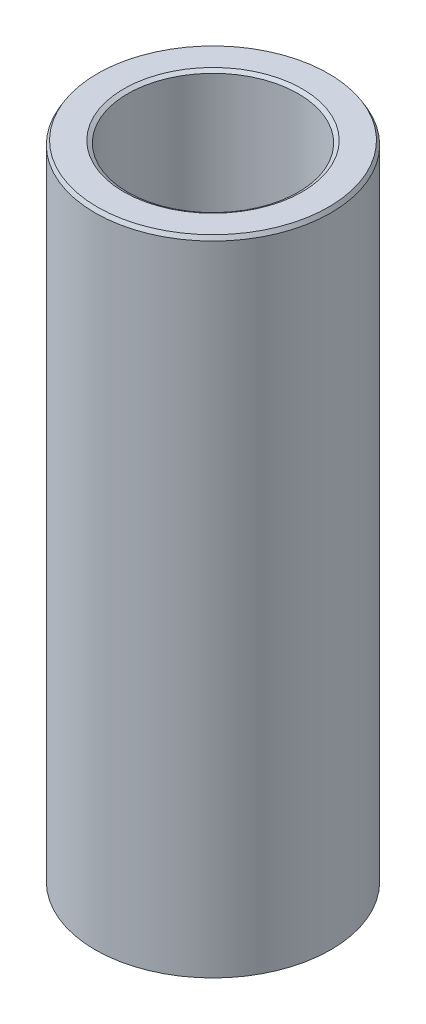
SolidWorks part; units mm, degrees
ref_plane "Front Plane" through (0, 0, 0) normal (0, 0, 1) x (1, 0, 0)
ref_plane "Top Plane" through (0, 0, 0) normal (0, 1, 0) x (1, 0, 0)
ref_plane "Right Plane" through (0, 0, 0) normal (1, 0, 0) x (0, 0, -1)
sketch "Sketch1" plane through (0, 0, 0) normal (0, 1, 0) x (1, 0, 0)
  circle A0 centre (0, 0) radius 45
  dimension "SLEEVE_OD" = 90
extrude "Boss-Extrude1" add sketch "Sketch1" along normal blind 245.9722
sketch "Sketch2" plane through (0, 0, 0) normal (0, 1, 0) x (1, 0, 0)
  circle A0 centre (0, 0) radius 32.5747
  dimension "BORE_D" = 65.1495
extrude "Cut-Extrude1" cut sketch "Sketch2" along normal through all
chamfer "Chamfer1" distance 1.5011 angle 30 4 edges at (0, 245.9722, 32.5747) (0, 0, 32.5747) (0, 0, 45) (0, 245.9722, 45) first distance on face at (0, 245.9722, 32.5747) first distance on face at (0, 0, 32.5747) first distance on face at (0, 245.9722, 45)
